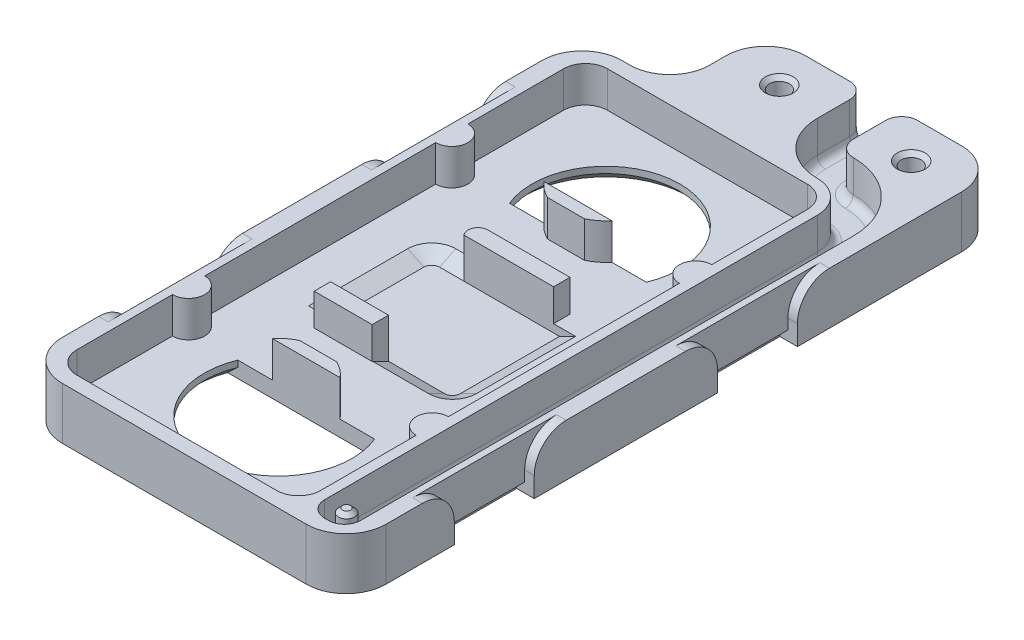
SolidWorks part; units mm, degrees
ref_plane "Front Plane" through (0, 0, 0) normal (0, 0, 1) x (1, 0, 0)
ref_plane "Top Plane" through (0, 0, 0) normal (0, 1, 0) x (1, 0, 0)
ref_plane "Right Plane" through (0, 0, 0) normal (1, 0, 0) x (0, 0, -1)
sketch "Sketch1" plane through (0, 0, 0) normal (0, 1, 0) x (1, 0, 0)
  line L0 (-16.5, 0) -> (16.5, 0) construction
  line L2 (-15, 0) -> (-15, 13.75)
  line L3 (-12.5, 32.5) -> (12.5, 32.5)
  line L4 (15, 0) -> (15, 6)
  line L7 (15, 9) -> (15, 13.75)
  line L8 (15, 9) -> (-3, 9)
  line L9 (15, 18.75) -> (15, 30)
  line L10 (15, 6) -> (-3, 6)
  line L11 (-15, 18.75) -> (-15, 30)
  line L12 (-15, -18.75) -> (-15, -30)
  line L13 (-15, 0) -> (-15, -6)
  line L14 (15, -18.75) -> (15, -30)
  line L15 (12.5, -32.5) -> (-12.5, -32.5)
  line L16 (-15, -9) -> (3, -9)
  line L17 (15, 0) -> (15, -13.75)
  line L18 (-15, -6) -> (3, -6)
  line L19 (-15, -9) -> (-15, -13.75)
  circle A0 centre (0, 20.5) radius 8.25
  arc A1 (15, 18.75) -> (15, 13.75) centre (15, 16.25) ccw
  arc A2 (-3, 9) -> (-3, 6) centre (-3, 7.5) ccw
  arc A3 (12.5, 32.5) -> (15, 30) centre (12.5, 30) cw
  arc A4 (-15, 30) -> (-12.5, 32.5) centre (-12.5, 30) cw
  arc A5 (-15, 13.75) -> (-15, 18.75) centre (-15, 16.25) ccw
  arc A6 (-12.5, -32.5) -> (-15, -30) centre (-12.5, -30) cw
  circle A7 centre (0, -20.5) radius 8.25
  arc A8 (3, -9) -> (3, -6) centre (3, -7.5) ccw
  arc A9 (15, -13.75) -> (15, -18.75) centre (15, -16.25) ccw
  arc A10 (-15, -18.75) -> (-15, -13.75) centre (-15, -16.25) ccw
  arc A11 (15, -30) -> (12.5, -32.5) centre (12.5, -30) cw
  point P23 (15, 32.5)
  point P26 (-15, 32.5)
  dimension "D4" = 16.5
  dimension "D5" = 5
  dimension "D6" = 16.5
  dimension "D10" = 2.5
  dimension "D11" = 65
  dimension "D15" = 2.5
  dimension "D1" = 30
  dimension "D2" = 6
  dimension "D3" = 12
  dimension "D7" = 3
  dimension "D8" = 32.5
  dimension "D9" = 12
  dimension "D12" = 3
  dimension "D13" = 16.25
  dimension "D14" = 12
  dimension "D16" = 16.25
sketch "Sketch2" plane through (0, 0, 0) normal (0, 1, 0) x (1, 0, 0)
  line L48 (15, 0) -> (15, 6) construction
  line L65 (17.5, -30) -> (17.5, 30)
  line L70 (12.5, 35) -> (-12.5, 35)
  line L71 (-17.5, 30) -> (-17.5, -30)
  line L78 (-12.5, -35) -> (12.5, -35)
  arc A0 (15, 30) -> (12.5, 32.5) centre (12.5, 30) ccw construction
  arc A1 (-12.5, 32.5) -> (-15, 30) centre (-12.5, 30) ccw construction
  arc A2 (-15, -30) -> (-12.5, -32.5) centre (-12.5, -30) ccw construction
  arc A3 (12.5, -32.5) -> (15, -30) centre (12.5, -30) ccw construction
  arc A42 (17.5, 30) -> (12.5, 35) centre (12.5, 30) ccw
  arc A43 (-12.5, 35) -> (-17.5, 30) centre (-12.5, 30) ccw
  arc A47 (-17.5, -30) -> (-12.5, -35) centre (-12.5, -30) ccw
  arc A48 (12.5, -35) -> (17.5, -30) centre (12.5, -30) ccw
  dimension "D1" = 2.5
extrude "Boss-Extrude1" add sketch "Sketch2" against normal blind 2
sketch "Sketch3" plane through (0, 0, 0) normal (0, 1, 0) x (-1, 0, 0)
  line L0 (15.25, 6.7) -> (0, 6.7)
  line L1 (15, 6) -> (-3, 6) construction
  line L2 (-15.25, -6.7) -> (3.9605, -6.7)
  line L3 (-15, -6) -> (3, -6) construction
  line L6 (-12.5, 33.2) -> (12.5, 33.2)
  line L7 (-12.5, 32.5) -> (12.5, 32.5) construction
  line L8 (-12.5, -33.2) -> (12.5, -33.2)
  line L9 (12.5, -32.5) -> (-12.5, -32.5) construction
  line L20 (-17.5, 30) -> (-17.5, -30)
  line L21 (12.5, 35) -> (-12.5, 35)
  line L22 (17.5, -30) -> (17.5, 30)
  line L23 (-12.5, -35) -> (12.5, -35)
  line L24 (-17.5, 30) -> (-17.5, -30)
  line L25 (12.5, 35) -> (-12.5, 35)
  line L26 (17.5, -30) -> (17.5, 30)
  line L27 (-12.5, -35) -> (12.5, -35)
  line L32 (-15.25, 30) -> (-15.25, 18.4861)
  line L33 (12.5, 32.75) -> (-12.5, 32.75)
  line L34 (15.25, 18.4861) -> (15.25, 30)
  line L35 (15.25, 8.75) -> (15.25, 14.0139)
  line L36 (-3, 8.75) -> (15.25, 8.75)
  line L37 (15.25, 6.25) -> (-3, 6.25)
  line L38 (15.25, 0) -> (15.25, 6.25)
  line L39 (15.25, -14.0139) -> (15.25, 0)
  line L40 (15.25, -30) -> (15.25, -18.4861)
  line L41 (-12.5, -32.75) -> (12.5, -32.75)
  line L42 (-15.25, -18.4861) -> (-15.25, -30)
  line L43 (-15.25, -8.75) -> (-15.25, -14.0139)
  line L44 (3, -8.75) -> (-15.25, -8.75)
  line L45 (-15.25, -6.25) -> (3, -6.25)
  line L46 (-15.25, 0) -> (-15.25, -6.25)
  line L47 (-15.25, 14.0139) -> (-15.25, 0)
  line L48 (-15.25, 30.45) -> (-15.25, 18.4861)
  line L50 (15.25, 18.4861) -> (15.25, 30.45)
  line L51 (15.25, 8.75) -> (15.25, 14.45)
  line L52 (0, 8.75) -> (15.25, 8.75)
  line L53 (0, 8.75) -> (0, 6.7)
  line L54 (15.25, 0) -> (15.25, 6.7)
  line L55 (15.25, -14.45) -> (15.25, 0)
  line L56 (15.25, -30.45) -> (15.25, -18.4861)
  line L58 (-15.25, -18.4861) -> (-15.25, -30.45)
  line L59 (-15.25, -8.75) -> (-15.25, -14.45)
  line L60 (3, -8.75) -> (-15.25, -8.75)
  line L62 (-15.25, 0) -> (-15.25, -6.7)
  line L63 (-15.25, 14.45) -> (-15.25, 0)
  arc A0 (-15.25, 14.45) -> (-15.25, 18.4861) centre (-15.25, 16.468) ccw
  arc A1 (15.25, 18.4861) -> (15.25, 14.45) centre (15.25, 16.468) ccw
  arc A2 (12.5, 33.2) -> (15.25, 30.45) centre (12.5, 30.45) cw
  arc A3 (-12.5, 33.2) -> (-15.25, 30.45) centre (-12.5, 30.45) ccw
  arc A4 (12.5, -33.2) -> (15.25, -30.45) centre (12.5, -30.45) ccw
  arc A5 (-15.25, -30.45) -> (-12.5, -33.2) centre (-12.5, -30.45) ccw
  arc A7 (15.25, -14.45) -> (15.25, -18.4861) centre (15.25, -16.468) ccw
  arc A8 (-15.25, -18.4861) -> (-15.25, -14.45) centre (-15.25, -16.468) ccw
  arc A14 (-17.5, -30) -> (-12.5, -35) centre (-12.5, -30) ccw
  arc A15 (-12.5, 35) -> (-17.5, 30) centre (-12.5, 30) ccw
  arc A16 (17.5, 30) -> (12.5, 35) centre (12.5, 30) ccw
  arc A17 (12.5, -35) -> (17.5, -30) centre (12.5, -30) ccw
  arc A18 (-17.5, -30) -> (-12.5, -35) centre (-12.5, -30) ccw
  arc A19 (-12.5, 35) -> (-17.5, 30) centre (-12.5, 30) ccw
  arc A20 (-12.5, 32.75) -> (-15.25, 30) centre (-12.5, 30) ccw
  arc A21 (15.25, 30) -> (12.5, 32.75) centre (12.5, 30) ccw
  arc A22 (15.25, 18.4861) -> (15.25, 14.0139) centre (15, 16.25) ccw
  arc A23 (-3, 8.75) -> (-3, 6.25) centre (-3, 7.5) ccw
  arc A24 (15.25, -14.0139) -> (15.25, -18.4861) centre (15, -16.25) ccw
  arc A25 (12.5, -32.75) -> (15.25, -30) centre (12.5, -30) ccw
  arc A26 (-15.25, -30) -> (-12.5, -32.75) centre (-12.5, -30) ccw
  arc A27 (-15.25, -18.4861) -> (-15.25, -14.0139) centre (-15, -16.25) ccw
  arc A28 (3, -8.75) -> (3, -6.25) centre (3, -7.5) ccw
  arc A29 (-15.25, 14.0139) -> (-15.25, 18.4861) centre (-15, 16.25) ccw
  arc A37 (3, -8.75) -> (3, -6.25) centre (3, -7.5) ccw
  arc A38 (3, -8.75) -> (3.9605, -6.7) centre (3, -7.5) ccw
  arc A40 (17.5, 30) -> (12.5, 35) centre (12.5, 30) ccw
  arc A41 (12.5, -35) -> (17.5, -30) centre (12.5, -30) ccw
  dimension "D7" = 2.75
  dimension "D10" = 2.75
  dimension "D3" = 0.7
  dimension "D4" = 0.7
  dimension "D5" = 0.7
  dimension "D6" = 0.7
  dimension "D8" = 0.7
  dimension "D9" = 0.7
  dimension "D11" = 0.7
  dimension "D12" = 0.7
  dimension "D1" = 0.25
  dimension "D2" = 0
  dimension "D13" = 0.25
extrude "Boss-Extrude2" add sketch "Sketch3" along normal blind 4.5
sketch "Sketch4" plane through (0, 0, 0) normal (0, 1, 0) x (1, 0, 0)
  line L7 (-8.5623, 17) -> (8.5623, 17)
  line L8 (-3.3, 0) -> (3.3, 0) construction
  line L9 (-8.5623, -17) -> (8.5623, -17)
  circle A13 centre (0, 20.5) radius 9.25
  arc A14 (8.5623, 17) -> (-8.5623, 17) centre (0, 20.5) ccw
  circle A16 centre (0, -20.5) radius 9.25
  arc A17 (-8.5623, -17) -> (8.5623, -17) centre (0, -20.5) ccw
  dimension "D1" = 17
  dimension "D2" = 17
  dimension "D3" = 1
  dimension "D4" = 1
extrude "Cut-Extrude1" cut sketch "Sketch4" against normal mid plane 14
chamfer "Chamfer1" distance 1.2 angle 45 2 edges at (0, -2, 29.75) (0, -2, -29.75)
sketch "Sketch6" plane through (0, 0, 0) normal (0, 1, 0) x (1, 0, 0)
  line L0 (15.25, 6.7) -> (-3.9605, 6.7) construction
  line L1 (8, 6.7) -> (-8, 6.7)
  line L2 (8, 6.7) -> (8, -6.7)
  line L3 (8, -6.7) -> (-8, -6.7)
  line L4 (-8, 6.7) -> (-8, -6.7)
  line L5 (-15.25, -6.7) -> (0, -6.7) construction
  line L6 (0, -1.1) -> (0, 1.1) construction
  dimension "D1" = 8
  dimension "D2" = 16
extrude "Cut-Extrude2" cut sketch "Sketch6" against normal blind 1
fillet "Fillet1" radius 1 2 edges at (8, -0.5, 6.7) (-8, -0.5, -6.7)
chamfer "Chamfer2" distance 2 distance2 1 6 edges at (8, 0, -0.5) (7.7071, 0, 6.4071) (3.5, 0, 6.7) (-8, 0, 0.5) (-7.7071, 0, -6.4071) (-5.4802, 0, -6.7) first distance on face at (1.5471, 0, 14.5146) first distance on face at (-2.0546, 0, -14.5349)
sketch "Sketch9" plane through (0, 0, 0) normal (0, 1, 0) x (1, 0, 0)
  line L0 (8.5623, -17) -> (-8.5623, -17) construction
  line L1 (4.2426, -17) -> (-4.2426, -17)
  line L2 (-8.5623, 17) -> (8.5623, 17) construction
  line L3 (-4.2426, 17) -> (4.2426, 17)
  line L4 (-2.2913, 15.5) -> (2.2913, 15.5)
  line L5 (2.2913, -15.5) -> (-2.2913, -15.5)
  line L6 (-8.5623, 17) -> (8.5623, 17) construction
  line L7 (-8.5623, 15.5) -> (8.5623, 15.5) construction
  line L8 (8.5623, -15.5) -> (-8.5623, -15.5) construction
  line L9 (8.5623, -17) -> (-8.5623, -17) construction
  arc A2 (-1.2839, -15.152) -> (1.2839, -15.152) centre (0, -20.5) ccw
  arc A3 (-2.2913, -15.5) -> (-4.2426, -17) centre (0, -20.5) ccw
  arc A4 (4.2426, -17) -> (2.2913, -15.5) centre (0, -20.5) ccw
  arc A6 (-4.2426, 17) -> (-2.2913, 15.5) centre (0, 20.5) ccw
  arc A7 (1.2839, 15.152) -> (-1.2839, 15.152) centre (0, 20.5) ccw
  arc A8 (2.2913, 15.5) -> (4.2426, 17) centre (0, 20.5) ccw
  dimension "D1" = 1.5
  dimension "D2" = 0.5
  dimension "D3" = 0.5
extrude "Boss-Extrude4" add sketch "Sketch9" along normal up to surface (4.5 mm away) up to face at (0, 4.5, 0)
ref_plane "Plane1" through (23, 0, 0) normal (1, 0, 0) x (0, 0, -1)
sketch "Sketch10" plane through (0, 0, 0) normal (1, 0, 0) x (0, 0, -1)
  line L0 (35, -2) -> (35, 4.5) construction
  line L1 (35, -2) -> (35, 4.5)
  line L2 (35, 4.5) -> (47, 4.5)
  line L3 (47, 4.5) -> (47, -2)
  line L4 (47, -2) -> (35, -2)
  line L5 (35, -2) -> (35.0281, -1.9905)
  dimension "D1" = 12
extrude "Boss-Extrude5" add sketch "Sketch10" along normal blind 4 and the other way blind 6.5 contours L4 L3 L2 L1 region at (0, 1.25, -41)
sketch "Sketch7" plane through (23, 0, 0) normal (1, 0, 0) x (0, 0, -1)
  line L0 (-35, -2) -> (-35, 4.5) construction
  line L1 (-35, -2) -> (-35, 4.5)
  line L2 (-30, 4.5) -> (30, 4.5) construction
  line L3 (-35, 4.5) -> (47, 4.5)
  line L4 (-30, -2) -> (30, -2) construction
  line L5 (-35, -2) -> (47, -2)
  line L7 (47, 4.5) -> (47, -2) construction
  line L8 (47, 4.5) -> (47, -2)
extrude "Boss-Extrude3" add sketch "Sketch7" against normal up to next
sketch "Sketch8" plane through (0, 4.5, 0) normal (0, 1, 0) x (1, 0, 0)
  line L1 (16.5, -33.2) -> (21, -33.2)
  line L2 (16.5, -33.2) -> (16.5, 30.45)
  line L3 (10.5, 49) -> (6, 49)
  line L4 (21, -33.2) -> (21, 30.45)
  line L6 (-12.5, -33.2) -> (12.5, -33.2) construction
  line L8 (18.75, -30.7) -> (18.75, -33.2) construction
  line L9 (6, 40.95) -> (6, 49)
  line L10 (23, -3.575) -> (23, 3.575) construction
  line L11 (10.5, 40.95) -> (10.5, 49)
  line L12 (23, 47) -> (-6.5, 47) construction
  circle A0 centre (18.75, -30.7) radius 1
  arc A2 (6, 40.95) -> (12.5, 34.45) centre (12.5, 40.95) ccw
  arc A3 (16.5, 30.45) -> (12.5, 34.45) centre (12.5, 30.45) ccw
  arc A4 (16.5, 30.45) -> (12.5, 34.45) centre (12.5, 30.45) ccw
  arc A5 (21, 30.45) -> (12.5, 38.95) centre (12.5, 30.45) ccw
  arc A6 (21, 30.45) -> (12.5, 38.95) centre (12.5, 30.45) ccw construction
  arc A7 (12.5, 38.95) -> (10.5, 40.95) centre (12.5, 40.95) cw
  dimension "D4" = 2
  dimension "D5" = 1.5
  dimension "D8" = 2
  dimension "D2" = 4.5
  dimension "D1" = 4.5
  dimension "D3" = 1.25
  dimension "D7" = 2
  dimension "D6" = 2
extrude "Cut-Extrude3" cut sketch "Sketch8" against normal offset from surface (5 mm away) 1.5 up to face at (0, -2, 23.975)
fillet "Fillet2" radius 2 2 edges at (16.5, 2, 33.2) (21, 2, 33.2)
fillet "Fillet3" radius 1 11 edges at (16.5, -0.5, 0.375) (17.0858, -0.5, 32.6142) (18.75, -0.5, 33.2) (20.4142, -0.5, 32.6142) (21, -0.5, 0.375) (10.5, -0.5, -43.975) (11.0858, -0.5, -39.5358) (18.5104, -0.5, -36.4604) (6, -0.5, -43.975) (7.9038, -0.5, -36.3538) (15.3284, -0.5, -33.2784)
fillet "Fillet5" radius 5 4 edges at (23, 1.25, 35) (23, 1.25, -47) (-6.5, 1.25, -47) (-6.5, 1.25, -35)
sketch "Sketch12" plane through (0, 4.5, 0) normal (0, 1, 0) x (1, 0, 0)
  line L0 (0, -3.575) -> (0, 3.575) construction
  line L4 (12.5, 33.2) -> (-12.5, 33.2) construction
  circle A0 centre (0, 42.2) radius 1.25
  circle A1 centre (16.5, 42.2) radius 1.25
  dimension "D1" = 2.5
  dimension "D3" = 9
  dimension "D4" = 16.5
extrude "Cut-Extrude4" cut sketch "Sketch12" against normal through all
sketch "Sketch13" plane through (0, 4.5, 0) normal (0, 1, 0) x (1, 0, 0)
  line L0 (8, 6.7) -> (-3.9605, 6.7) construction
  line L1 (15.25, 8.75) -> (7.25, 8.75)
  line L2 (15.25, 8.75) -> (15.25, 6.7)
  line L3 (15.25, 6.7) -> (7.25, 6.7)
  line L4 (7.25, 8.75) -> (7.25, 6.7)
  line L5 (0, -8.75) -> (-15.25, -8.75) construction
  line L6 (-15.25, -6.7) -> (-7.25, -6.7)
  line L7 (-15.25, -6.7) -> (-15.25, -8.75)
  line L8 (-15.25, -8.75) -> (-7.25, -8.75)
  line L9 (-7.25, -6.7) -> (-7.25, -8.75)
  dimension "D1" = 8
  dimension "D2" = 8
extrude "Cut-Extrude5" cut sketch "Sketch13" against normal up to surface (4.5 mm away) up to face at (1.8414, 0, 14.8088)
sketch "Sketch14" plane through (0, 4.5, 0) normal (0, 1, 0) x (1, 0, 0)
  line L0 (-17.5, 30) -> (-17.5, -30) construction
  line L1 (-17.5, 21.468) -> (-16.3, 21.468)
  line L2 (-17.5, 21.468) -> (-17.5, 11.468)
  line L3 (-17.5, 11.468) -> (-16.3, 11.468)
  line L4 (-16.3, 21.468) -> (-16.3, 11.468)
  line L5 (-17.5, 16.468) -> (-15.25, 16.468) construction
  line L6 (-17.5, -11.468) -> (-16.3, -11.468)
  line L7 (-17.5, -11.468) -> (-17.5, -21.468)
  line L8 (-17.5, -21.468) -> (-16.3, -21.468)
  line L9 (-16.3, -11.468) -> (-16.3, -21.468)
  line L10 (-17.5, -16.468) -> (-15.25, -16.468) construction
  dimension "D1" = 1.2
  dimension "D2" = 10
extrude "Cut-Extrude6" cut sketch "Sketch14" against normal through all
sketch "Sketch15" plane through (-16.3, 0, 0) normal (-1, 0, 0) x (0, 0, 1)
  line L0 (-11.468, -2) -> (-11.468, 4.5) construction
  line L1 (-21.468, -2) -> (-11.468, -2)
  line L2 (-21.468, -2) -> (-21.468, -0.8)
  line L3 (-21.468, -0.8) -> (-11.468, -0.8)
  line L4 (-11.468, -2) -> (-11.468, -0.8)
  line L5 (21.468, -2) -> (21.468, 4.5) construction
  line L6 (11.468, -2) -> (21.468, -2)
  line L7 (11.468, -2) -> (11.468, -0.8)
  line L8 (11.468, -0.8) -> (21.468, -0.8)
  line L9 (21.468, -2) -> (21.468, -0.8)
  dimension "D1" = 1.2
extrude "Cut-Extrude7" cut sketch "Sketch15" against normal blind 1
ref_plane "Plane3" through (2.75, 0, 0) normal (-1, 0, 0) x (0, 0, 1)
mirror "Mirror1" about plane through (2.75, 0, 0) normal (-1, 0, 0) of "Cut-Extrude7", "Cut-Extrude6"
fillet "Fillet6" radius 4 8 edges at (-16.9, 4.5, -21.468) (-16.9, 4.5, -11.468) (-16.9, 4.5, 11.468) (-16.9, 4.5, 21.468) (22.4, 4.5, -21.468) (22.4, 4.5, -11.468) (22.4, 4.5, 11.468) (22.4, 4.5, 21.468)
fillet "Fillet7" radius 2 5 edges at (10.5, 2.5, -47) (10.2071, -0.2071, -47) (6, 2.5, -47) (6.2929, -0.2071, -47) (8.25, -0.5, -47)
sketch "Sketch16" plane through (-17.5, 0, 0) normal (-1, 0, 0) x (0, 0, 1)
  line L0 (-22.8223, 3.5) -> (-10.1138, 3.5)
  line L1 (10.1138, 3.5) -> (22.8223, 3.5)
  line L4 (-21.468, 0.5) -> (-21.468, -0.8)
  line L5 (-21.468, -0.8) -> (-11.468, -0.8)
  line L6 (-11.468, -0.8) -> (-11.468, 0.5)
  line L7 (-7.468, 4.5) -> (-25.468, 4.5)
  line L11 (-7.468, 4.5) -> (-25.468, 4.5)
  line L13 (11.468, 0.5) -> (11.468, -0.8)
  line L14 (11.468, -0.8) -> (21.468, -0.8)
  line L15 (21.468, -0.8) -> (21.468, 0.5)
  line L16 (25.468, 4.5) -> (7.468, 4.5)
  line L20 (25.468, 4.5) -> (7.468, 4.5)
  arc A2 (-7.468, 4.5) -> (-11.468, 0.5) centre (-7.468, 0.5) ccw
  arc A3 (-21.468, 0.5) -> (-25.468, 4.5) centre (-25.468, 0.5) ccw
  arc A4 (-7.468, 4.5) -> (-10.1138, 3.5) centre (-7.468, 0.5) ccw
  arc A5 (-22.8223, 3.5) -> (-25.468, 4.5) centre (-25.468, 0.5) ccw
  arc A6 (25.468, 4.5) -> (21.468, 0.5) centre (25.468, 0.5) ccw
  arc A7 (11.468, 0.5) -> (7.468, 4.5) centre (7.468, 0.5) ccw
  arc A8 (25.468, 4.5) -> (22.8223, 3.5) centre (25.468, 0.5) ccw
  arc A9 (10.1138, 3.5) -> (7.468, 4.5) centre (7.468, 0.5) ccw
  dimension "D3" = 1
  dimension "D1" = 0
  dimension "D2" = 0
sketch "Sketch17" plane through (0, 0, -8.75) normal (0, 0, -1) x (-1, 0, 0)
  line L0 (-6, 4.5) -> (-12.5, 4.5) construction
  line L1 (-8.8223, 4.5) -> (8.7025, 4.5)
  line L2 (-8.8223, 4.5) -> (-8.8223, 4)
  line L3 (-8.8223, 4) -> (8.7025, 4)
  line L4 (8.7025, 4.5) -> (8.7025, 4)
  dimension "D1" = 0.5
extrude "Cut-Extrude9" cut sketch "Sketch17" against normal up to surface (17.5 mm away) up to face at (-3.625, 2.25, 8.75)
chamfer "Chamfer3" distance 0.5 angle 45 2 edges at (0, 4.5, -40.95) (16.5, 4.5, -40.95)
chamfer "Chamfer4" distance 0.5 angle 45 1 edges at (18.75, 4.5, 31.7)
